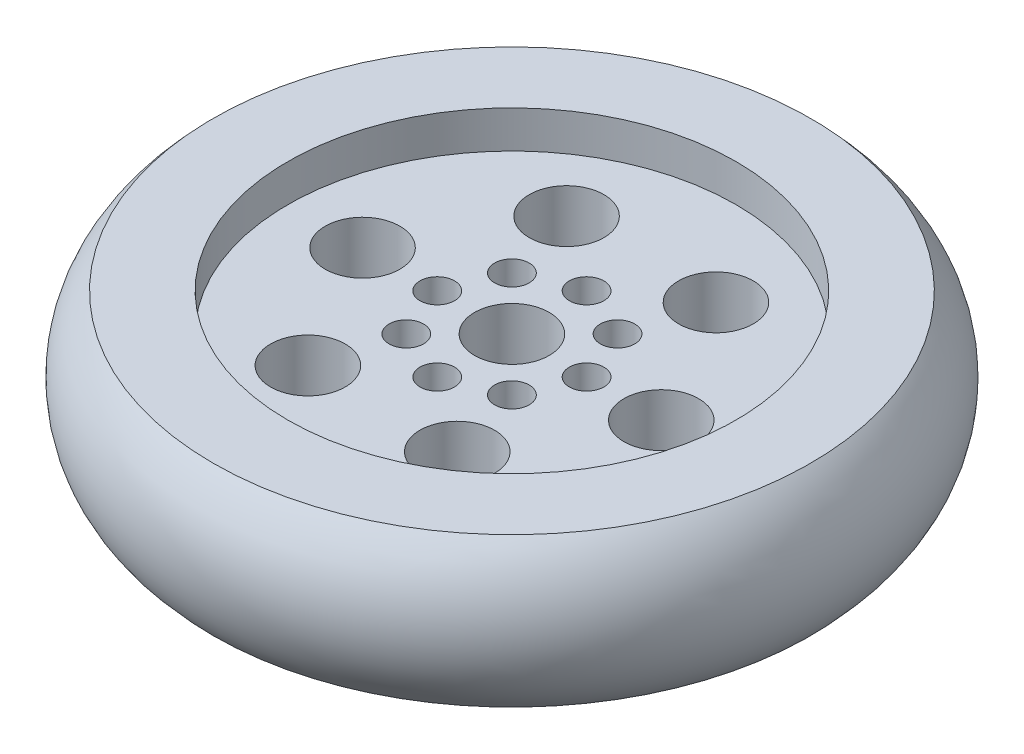
SolidWorks part; units mm, degrees
ref_plane "前视基准面" through (0, 0, 0) normal (0, 0, 1) x (1, 0, 0)
ref_plane "上视基准面" through (0, 0, 0) normal (0, 1, 0) x (1, 0, 0)
ref_plane "右视基准面" through (0, 0, 0) normal (1, 0, 0) x (0, 0, -1)
sketch "草图1" plane through (0, 0, 0) normal (0, 1, 0) x (1, 0, 0)
  line L0 (-61.7183, 0) -> (73.1255, 0) construction
  line L1 (0, 54.0567) -> (0, -60.0157) construction
  circle A0 centre (0, 0) radius 24
  circle A1 centre (0, 0) radius 32
  circle A2 centre (16, 0) radius 4
  circle A3 centre (8, -13.8564) radius 4
  circle A4 centre (-8, -13.8564) radius 4
  circle A5 centre (-16, 0) radius 4
  circle A6 centre (-8, 13.8564) radius 4
  circle A7 centre (8, 13.8564) radius 4
  point P22 (0, 0)
  line B0 (-21.2209, 0) -> (20.4538, 0) construction
  line B1 (0, 15.6919) -> (0, -15.9476) construction
  circle B2 centre (0, 0) radius 4
  circle B3 centre (8, 0) radius 1.85
  circle B4 centre (5.6569, -5.6569) radius 1.85
  circle B5 centre (0, -8) radius 1.85
  circle B6 centre (-5.6569, -5.6569) radius 1.85
  circle B7 centre (-8, 0) radius 1.85
  circle B8 centre (-5.6569, 5.6569) radius 1.85
  circle B9 centre (0, 8) radius 1.85
  circle B10 centre (5.6569, 5.6569) radius 1.85
  dimension "D1" = 8
  dimension "D4" = 48
  dimension "D5" = 64
  dimension "D2" = 16
  dimension "D3" = 6
sketch_block_instance "块-星形8孔-1"
sketch_block "块-星形8孔" parameters "D1"=8, "D3"=3.7, "D2"=8
extrude "wheel hub tap" add sketch "草图1" along normal mid plane 8 contours A0 B10 B9 B8 B7 B6 B5 B4 B3 B2 A7 A6 A5 A4 A3 A2 region at (-23.3212, 0, 0)
extrude "wheel hub outside" add sketch "草图1<3>" along normal mid plane 16 separate body contours A1 A0 region at (-31.0949, 0, 0)
sketch "草图1<3>" plane through (0, 0, 0) normal (0, 1, 0) x (1, 0, 0) same geometry as "草图1"
sketch "草图2" plane through (0, 0, 0) normal (1, 0, 0) x (0, 0, -1)
  line L0 (32, 8) -> (32, -8)
  arc A0 (32, 8) -> (32, -8) centre (24, 0) cw
ref_axis "中心轴" through (0, 67.1102, 0) along (0, -1, 0)
revolve "rubber tyre" add sketch "草图2" angle 360 about axis through (0, 67.1102, 0) along (0, -1, 0)
